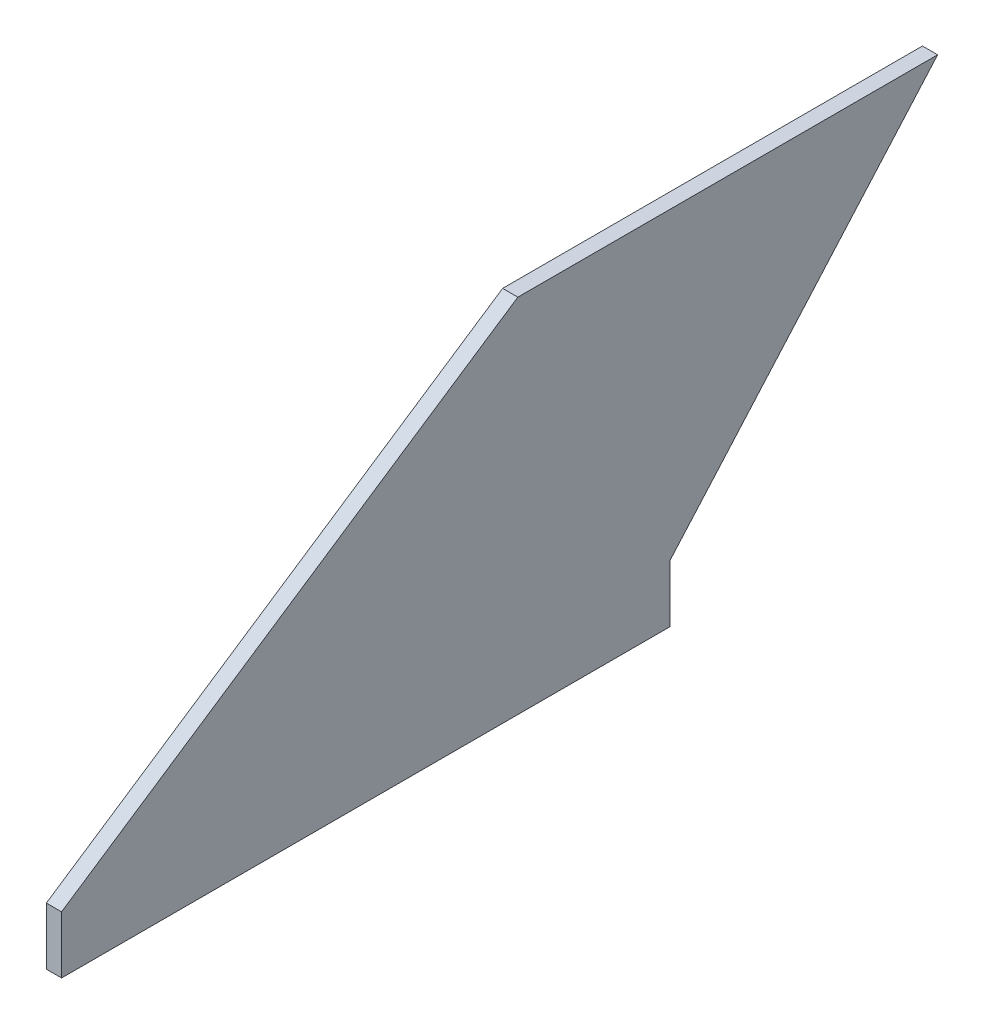
SolidWorks part; units mm, degrees
ref_plane "Front Plane" through (0, 0, 0) normal (0, 0, 1) x (1, 0, 0)
ref_plane "Top Plane" through (0, 0, 0) normal (0, 1, 0) x (1, 0, 0)
ref_plane "Right Plane" through (0, 0, 0) normal (1, 0, 0) x (0, 0, -1)
sketch "Sketch2" plane through (0, 0, 0) normal (1, 0, 0) x (0, 0, -1)
  line L0 (0, 0) -> (95.25, 63.5)
  line L1 (0, -11.9634) -> (127, -11.9634)
  line L2 (0, -11.9634) -> (0, 0)
  line L3 (0, 0) -> (127, 0) construction
  line L4 (127, -11.9634) -> (127, 0)
  line L5 (0, -11.9634) -> (127, 0) construction
  line L6 (0, 0) -> (127, -11.9634) construction
  line L7 (95.25, 63.5) -> (182.88, 63.5)
  line L8 (182.88, 63.5) -> (127, 0)
  point P0 (63.5, -5.9817)
  point P7 (0, 0)
  dimension "D1" = 95.25
  dimension "D2" = 63.5
  dimension "D3" = 182.88
  dimension "D4" = 127
  dimension "D5" = 11.9634
extrude "Boss-Extrude1" add sketch "Sketch2" along normal blind 3.175
